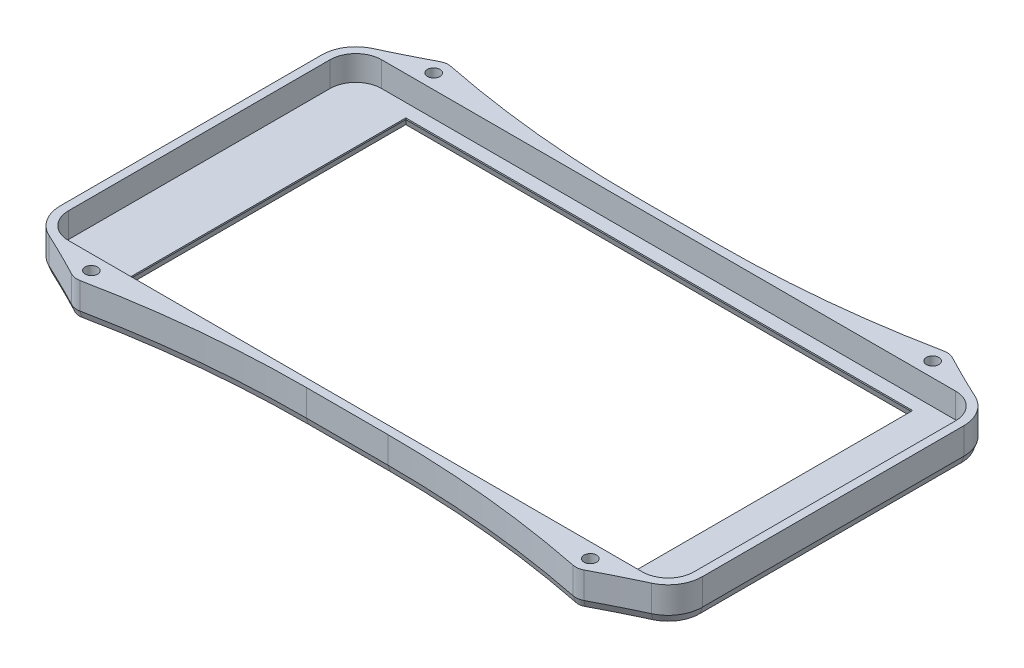
SolidWorks part; units mm, degrees
note: The reader was unsure of these and kept them because the rebuilt part matched: shared geometry of "草图1<5>", "草图6<2>", "草图10<5>".
ref_plane "前视基准面" through (0, 0, 0) normal (0, 0, 1) x (1, 0, 0)
ref_plane "上视基准面" through (0, 0, 0) normal (0, 1, 0) x (1, 0, 0)
ref_plane "右视基准面" through (0, 0, 0) normal (1, 0, 0) x (0, 0, -1)
sketch "草图1" plane through (0, 0, 0) normal (0, 1, 0) x (1, 0, 0)
  line L0 (6, 0.2) -> (143.8, 0.2)
  line L1 (6, 0) -> (143.8, 0) construction
  line L2 (0, -6) -> (0, -68.8) construction
  line L3 (6, -74.8) -> (143.8, -74.8) construction
  line L4 (149.8, -6) -> (149.8, -68.8) construction
  line L5 (150, -6) -> (150, -68.8)
  line L6 (6, -75) -> (143.8, -75)
  line L7 (-0.2, -6) -> (-0.2, -68.8)
  arc A0 (143.8, 0) -> (149.8, -6) centre (143.8, -6) cw construction
  arc A1 (143.8, -74.8) -> (149.8, -68.8) centre (143.8, -68.8) ccw construction
  arc A2 (0, -68.8) -> (6, -74.8) centre (6, -68.8) ccw construction
  arc A3 (6, 0) -> (0, -6) centre (6, -6) ccw construction
  arc A4 (143.8, 0.2) -> (150, -6) centre (143.8, -6) cw
  arc A5 (143.8, -75) -> (150, -68.8) centre (143.8, -68.8) ccw
  arc A6 (-0.2, -68.8) -> (6, -75) centre (6, -68.8) ccw
  arc A7 (6, 0.2) -> (-0.2, -6) centre (6, -6) ccw
  point P7 (149.8, 0)
  point P12 (0, -74.8)
  point P15 (0, 0)
  dimension "D3" = 6
  dimension "D1" = 74.8
  dimension "D2" = 149.8
  dimension "D4" = 0.2
extrude "凸台-拉伸1" add sketch "草图1" along normal blind 2
extrude "拉伸-薄壁2" add sketch "草图1<5>" along normal blind 8 thin thin type one direction wall 2
sketch "草图1<5>" plane through (0, 0, 0) normal (0, 1, 0) x (1, 0, 0) same geometry as "草图1"
sketch "草图6" plane through (0, 0, 0) normal (0, 1, 0) x (1, 0, 0)
  line L1 (0, -6) -> (0, -68.8) construction
  line L2 (149.8, -6) -> (149.8, -68.8) construction
  line L4 (6, 0.2) -> (143.8, 0.2) construction
  line L5 (6, -75) -> (143.8, -75) construction
  circle A0 centre (15, 3.7) radius 1.5
  circle A1 centre (15, -78.5) radius 1.5
  circle A2 centre (134.8, 3.7) radius 1.5
  circle A3 centre (134.8, -78.5) radius 1.5
  circle A4 centre (15, 3.7) radius 3.5
  circle A5 centre (15, -78.5) radius 3.5
  circle A6 centre (134.8, 3.7) radius 3.5
  circle A7 centre (134.8, -78.5) radius 3.5
  dimension "D1" = 3
  dimension "D4" = 15
  dimension "D5" = 15
  dimension "D2" = 2
extrude "凸台-拉伸10" add sketch "草图6" along normal up to surface (8 mm away) up to face at (74.9, 8, 37.4)
sketch "草图7" plane through (0, 0, 0) normal (0, -1, 0) x (-1, 0, 0)
  line L0 (0, -6) -> (0, -68.8) construction
  line L1 (-136.7, -3) -> (-15, -3)
  line L2 (-136.7, -3) -> (-136.7, -71.8)
  line L3 (-136.7, -71.8) -> (-15, -71.8)
  line L4 (-15, -3) -> (-15, -71.8)
  point P6 (0, -37.4)
  point P9 (-15, -37.4)
  dimension "D1" = 15
  dimension "D2" = 121.7
  dimension "D3" = 68.8
extrude "切除-拉伸1" cut sketch "草图7" against normal blind 10
sketch "草图8" plane through (0, 2, 0) normal (0, 1, 0) x (1, 0, 0)
  line L0 (143.8, 0.4) -> (6, 0.4)
  line L1 (-0.4, -6) -> (-0.4, -68.8)
  line L2 (6, -75.2) -> (143.8, -75.2)
  line L3 (150.2, -68.8) -> (150.2, -6)
  line L4 (143.8, 0.2) -> (6, 0.2)
  line L5 (150, -68.8) -> (150, -6)
  line L6 (6, -75) -> (143.8, -75)
  line L7 (-0.2, -6) -> (-0.2, -68.8)
  line L8 (143.8, 0.2) -> (6, 0.2) construction
  line L9 (150, -68.8) -> (150, -6) construction
  line L10 (6, -75) -> (143.8, -75) construction
  line L11 (-0.2, -6) -> (-0.2, -68.8) construction
  arc A0 (6, 0.4) -> (-0.4, -6) centre (6, -6) ccw
  arc A1 (-0.4, -68.8) -> (6, -75.2) centre (6, -68.8) ccw
  arc A2 (143.8, -75.2) -> (150.2, -68.8) centre (143.8, -68.8) ccw
  arc A3 (150.2, -6) -> (143.8, 0.4) centre (143.8, -6) ccw
  arc A4 (150, -6) -> (143.8, 0.2) centre (143.8, -6) ccw
  arc A5 (143.8, -75) -> (150, -68.8) centre (143.8, -68.8) ccw
  arc A6 (-0.2, -68.8) -> (6, -75) centre (6, -68.8) ccw
  arc A7 (6, 0.2) -> (-0.2, -6) centre (6, -6) ccw
  arc A8 (150, -6) -> (143.8, 0.2) centre (143.8, -6) ccw construction
  arc A9 (143.8, -75) -> (150, -68.8) centre (143.8, -68.8) ccw construction
  arc A10 (-0.2, -68.8) -> (6, -75) centre (6, -68.8) ccw construction
  arc A11 (6, 0.2) -> (-0.2, -6) centre (6, -6) ccw construction
  dimension "D1" = 0
  dimension "D2" = 0.2
extrude "切除-拉伸3" [suppressed] cut sketch "草图8" along normal blind 10.5
fillet "圆角1" radius 250 8 edges at (18.1623, 4, 77) (11.8377, 4, 77) (137.9623, 4, 77) (131.6377, 4, 77) (131.6377, 4, -2.2) (137.9623, 4, -2.2) (11.8377, 4, -2.2) (18.1623, 4, -2.2)
extrude "凸台-拉伸11" add sketch "草图6<2>" along normal blind 1.5 contours A1 | A3 | A2 | A0
sketch "草图6<2>" plane through (0, 0, 0) normal (0, 1, 0) x (1, 0, 0) same geometry as "草图6"
sketch "草图10" plane through (0, 0, 0) normal (0, -1, 0) x (1, 0, 0)
  line L0 (-0.9077, 33.8117) -> (1.1353, 33.8117) construction
  line L1 (13.829, 32.586) -> (12.4819, 32.586)
  line L2 (12.4819, 32.586) -> (6.1067, 38.9612)
  line L3 (6.1067, 38.9612) -> (-0.2684, 32.586)
  line L4 (-0.2684, 32.586) -> (-1.5033, 32.586)
  line L5 (-1.5033, 32.586) -> (5.5711, 39.6604)
  line L6 (5.5711, 39.6604) -> (5.5711, 41.4979)
  line L7 (5.8129, 41.7396) -> (8.8852, 41.7396)
  line L8 (8.8852, 41.1705) -> (6.5903, 41.1705)
  line L9 (6.5903, 41.1705) -> (6.5903, 39.6604)
  line L10 (6.5903, 39.6604) -> (13.829, 32.586)
  line L11 (13.829, 32.586) -> (13.829, 35.667)
  line L12 (13.829, 35.667) -> (8.3254, 41.1705)
  line L13 (-1.5033, 32.586) -> (-1.5033, 35.667)
  line L14 (-1.5033, 35.667) -> (3.9252, 41.0955)
  line L15 (3.9252, 41.0955) -> (5.5711, 41.0955)
  line L16 (12.805, 41.9734) -> (12.6471, 41.9734)
  line L17 (13.5026, 40.9899) -> (12.805, 40.9899)
  line L18 (13.5026, 40.9899) -> (13.5026, 44.4493)
  line L19 (13.5026, 44.4493) -> (12.805, 44.4493)
  line L20 (12.805, 40.9899) -> (12.805, 44.4493)
  line L21 (10.3524, 40.9899) -> (9.7989, 40.9899)
  line L22 (10.3524, 40.9899) -> (10.3524, 44.4493)
  line L23 (10.3524, 44.4493) -> (9.7989, 44.4493)
  line L24 (9.7989, 40.9899) -> (9.7989, 44.4493)
  line L25 (9.071, 42.1448) -> (8.6298, 42.1448)
  line L26 (9.071, 42.1448) -> (9.071, 44.4493)
  line L27 (9.071, 44.4493) -> (8.6298, 44.4493)
  line L28 (8.6298, 42.1448) -> (8.6298, 44.4493)
  line L29 (12.6471, 41.9734) -> (12.6471, 42.6121)
  line L30 (12.6471, 42.6121) -> (12.4289, 42.6121)
  line L31 (12.4289, 42.6121) -> (10.8346, 41.0179)
  line L32 (10.8346, 41.0179) -> (10.8346, 41.3346)
  line L33 (10.8346, 41.3346) -> (12.2196, 42.7196)
  line L34 (12.2196, 42.7196) -> (10.8069, 44.1323)
  line L35 (10.8069, 44.1323) -> (10.8069, 44.4493)
  line L36 (10.8069, 44.4493) -> (12.4289, 42.8273)
  line L37 (12.4289, 42.8273) -> (12.7261, 42.8273)
  line L38 (12.7261, 42.8273) -> (12.805, 42.7802)
  line L39 (12.6471, 42.234) -> (11.431, 41.0179)
  line L40 (11.431, 41.0179) -> (10.8346, 41.0179)
  line L41 (12.6471, 42.8273) -> (12.6471, 43.2288)
  line L42 (12.6471, 43.2288) -> (11.431, 44.4449)
  line L43 (11.431, 44.4449) -> (10.8069, 44.4493)
  line L44 (7.32, 42.5817) -> (7.32, 43.8942)
  line L45 (4.6596, 42.5818) -> (4.6596, 43.8942)
  line L46 (0.5537, 43.276) -> (2.2264, 43.276)
  line L48 (2.2054, 42.846) -> (1.1785, 42.846)
  line L49 (0.823, 43.8385) -> (0.6714, 44.2857)
  line L51 (7.2072, 44.4202) -> (7.32, 44.3922)
  line L52 (7.32, 44.3922) -> (7.32, 45.2349)
  line L53 (7.32, 45.2349) -> (7.8943, 45.2349)
  line L54 (7.8943, 45.2349) -> (7.8747, 42.1448)
  line L55 (4.6243, 44.3843) -> (4.6805, 44.4007)
  line L56 (4.6805, 44.4007) -> (4.6805, 45.2349)
  line L57 (4.6805, 45.2349) -> (5.2491, 45.2349)
  line L58 (5.2491, 45.2349) -> (5.2232, 42.1492)
  line L60 (-1.2643, 42.132) -> (-1.3026, 42.2469)
  line L61 (-1.3026, 42.2469) -> (-1.2643, 42.6121)
  line L62 (-1.2643, 42.6121) -> (-0.4215, 42.5917)
  line L63 (-0.4215, 42.5917) -> (-0.4577, 44.4493)
  line L64 (-0.4577, 44.4493) -> (0.1148, 44.4493)
  line L65 (0.1148, 44.4493) -> (0.1148, 42.2469)
  arc A0 (5.5711, 41.4979) -> (5.8129, 41.7396) centre (5.8129, 41.4979) cw
  arc A1 (8.8852, 41.7396) -> (8.8852, 41.1705) centre (8.8852, 41.4551) cw
  spline S0 degree 2 poles (1.6444, 44.4735) (1.1342, 44.4997) (0.6714, 44.2857) knots 0 0 0 1 1 1
  spline S1 degree 3 poles (7.8747, 42.1448) (7.498, 42.0515) (6.9053, 42.0207) (6.3799, 42.1623) (6.0087, 42.3911) (5.7719, 42.8836) (5.7839, 43.7586) (5.9881, 44.1766) (6.4539, 44.4396) (6.8373, 44.5059) (7.0498, 44.4549) (7.2072, 44.4202) knots 0 0 0 0 0.248699 0.269163 0.292864 0.485711 0.623698 0.822275 0.850786 0.908813 1 1 1 1
  spline S2 degree 3 poles (5.2232, 42.1492) (4.8465, 42.0558) (4.2535, 42.0242) (3.7312, 42.1662) (3.3807, 42.3735) (3.1131, 42.8917) (3.136, 43.7683) (3.3323, 44.1539) (3.793, 44.4276) (4.172, 44.5313) (4.4669, 44.419) (4.6243, 44.3843) knots 0 0 0 0 0.262042 0.283604 0.306987 0.495873 0.631025 0.825523 0.853466 0.910451 1 1 1 1
  spline S3 degree 3 poles (7.32, 42.5817) (7.0734, 42.4629) (6.4494, 42.5935) (6.3635, 43.246) (6.3645, 43.796) (6.8607, 44.0322) (7.2317, 43.9609) (7.32, 43.8942) knots 0 0 0 0 0.259398 0.39526 0.549468 0.696298 0.820989 0.820989 0.820989 0.820989
  spline S4 degree 3 poles (4.6596, 42.5818) (4.4131, 42.463) (3.789, 42.5935) (3.7031, 43.2461) (3.7042, 43.7961) (4.2004, 44.0323) (4.5713, 43.961) (4.6596, 43.8942) knots 0 0 0 0 0.259398 0.39526 0.549468 0.696298 0.820989 0.820989 0.820989 0.820989
  spline S5 degree 3 poles (0.1148, 42.2469) (-0.3434, 42.063) (-0.723, 42.0488) (-1.2643, 42.132) knots 0 0 0 0 0.886161 0.886161 0.886161 0.886161
  spline S6 degree 3 poles (1.6444, 44.4735) (1.7271, 44.4733) (1.8493, 44.4634) (2.0063, 44.429) (2.1163, 44.3922) (2.22, 44.3441) (2.319, 44.2875) (2.4115, 44.2189) (2.4974, 44.1404) (2.5763, 44.0537) (2.6443, 43.9581) (2.7016, 43.8547) (2.7492, 43.7441) (2.7861, 43.6254) (2.8204, 43.4527) (2.8301, 43.3179) (2.8302, 43.2262) knots 0 0 0 0 0.127973 0.188911 0.24826 0.307064 0.365585 0.424502 0.484814 0.545423 0.605641 0.66591 0.728019 0.791575 0.858016 1 1 1 1
  spline S7 degree 3 poles (2.8302, 43.2262) (2.8302, 43.1347) (2.8203, 43.0002) (2.7861, 42.8278) (2.7491, 42.709) (2.7018, 42.5982) (2.6431, 42.4952) (2.5759, 42.3987) (2.4965, 42.312) (2.4107, 42.2335) (2.3182, 42.1648) (2.2193, 42.1085) (2.1159, 42.0597) (2.0059, 42.0236) (1.8491, 41.9886) (1.7271, 41.9792) (1.6444, 41.9789) knots 0 0 0 0 0.14162 0.208078 0.27165 0.333775 0.394255 0.454817 0.515441 0.575767 0.634699 0.693235 0.751689 0.811434 0.871995 1 1 1 1
  spline S8 degree 3 poles (1.6444, 41.9789) (1.5667, 41.9787) (1.4522, 41.9874) (1.3051, 42.0188) (1.203, 42.0526) (1.1064, 42.0946) (1.0159, 42.1464) (0.932, 42.2087) (0.852, 42.2782) (0.7818, 42.3612) (0.7195, 42.4553) (0.6683, 42.5625) (0.6266, 42.6817) (0.5929, 42.813) (0.5616, 43.012) (0.5536, 43.1683) (0.5537, 43.276) knots 0 0 0 0 0.120486 0.17735 0.232867 0.286956 0.340345 0.394224 0.448695 0.504379 0.562228 0.623097 0.688048 0.757874 0.832941 1 1 1 1
  spline S9 degree 3 poles (2.2264, 43.276) (2.2274, 43.338) (2.2217, 43.4274) (2.2037, 43.5408) (2.1854, 43.6154) (2.1603, 43.6823) (2.131, 43.7423) (2.0956, 43.7945) (2.0417, 43.8529) (1.9662, 43.9122) (1.8325, 43.9834) (1.7193, 44.0023) (1.6444, 44.0021) knots 0 0 0 0 0.176057 0.253826 0.326137 0.393854 0.456561 0.515512 0.572451 0.681713 0.786683 1 1 1 1
  spline S10 degree 2 poles (1.6444, 44.0021) (1.215, 44.0115) (0.823, 43.8385) knots 0 0 0 1 1 1
  spline S11 degree 3 poles (1.1785, 42.846) (1.19, 42.782) (1.2179, 42.691) (1.2844, 42.5885) (1.3451, 42.5296) (1.4166, 42.4849) (1.5287, 42.4403) (1.622, 42.4295) (1.6857, 42.43) knots 0 0 0 0 0.269611 0.388375 0.502502 0.61712 0.735396 1 1 1 1
  spline S12 degree 3 poles (1.6857, 42.43) (1.739, 42.4301) (1.8189, 42.4422) (1.9189, 42.4822) (1.9905, 42.5247) (2.0577, 42.5809) (2.139, 42.6847) (2.1822, 42.7784) (2.2054, 42.846) knots 0 0 0 0 0.223314 0.334801 0.4501 0.571479 0.700127 1 1 1 1
extrude "切除-拉伸4" cut sketch "草图10" against normal blind 1.5 contours A1 L7 A0 L6 L5 L4 L3 L2 L1 L10 L9 L8 | L38 L37 L36 L35 L34 L33 L32 L31 L30 L29 L16 L20
extrude "切除-拉伸5" cut sketch "草图10<5>" against normal blind 0.6
sketch "草图10<5>" plane through (0, 0, 0) normal (0, -1, 0) x (1, 0, 0) same geometry as "草图10"
chamfer "倒角1" distance 0.6 angle 70 24 edges at (152, 0, 37.4) (150.7143, 0, 1.5917) (141.812, 0, -4.0506) (135.2971, 0, -7.1645) (109.5269, 0, -3.4358) (74.9, 0, -2.2) (40.2731, 0, -3.4358) (14.5029, 0, -7.1645) (7.988, 0, -4.0506) (-0.9143, 0, 1.5917) (-2.2, 0, 37.4) (-0.9143, 0, 73.2083) (7.988, 0, 78.8506) (14.5029, 0, 81.9645) (40.2731, 0, 78.2358) (74.9, 0, 77) (109.5269, 0, 78.2358) (135.2971, 0, 81.9645) (141.812, 0, 78.8506) (150.7143, 0, 73.2083) (15, 0, 37.4) (75.85, 0, 3) (136.7, 0, 37.4) (75.85, 0, 71.8)
